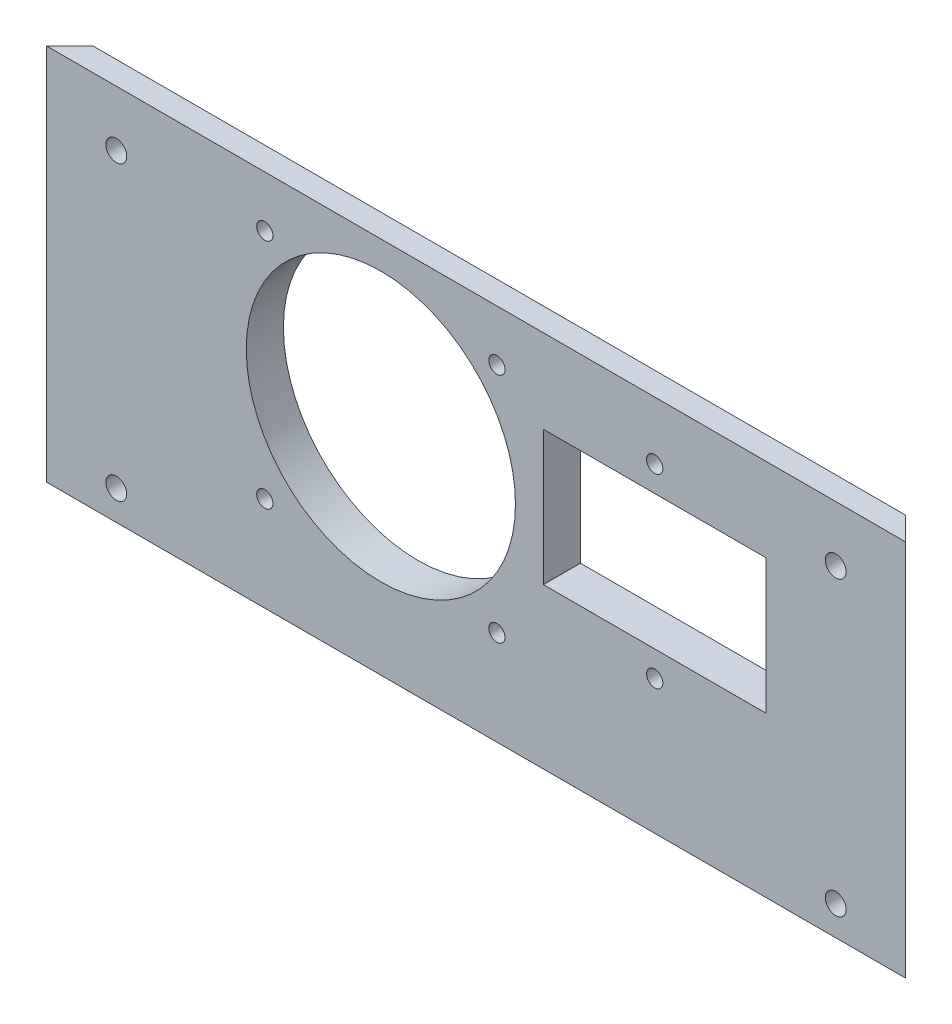
SolidWorks part; units mm, degrees
ref_plane "Front Plane" through (0, 0, 0) normal (0, 0, 1) x (1, 0, 0)
ref_plane "Top Plane" through (0, 0, 0) normal (0, 1, 0) x (1, 0, 0)
ref_plane "Right Plane" through (0, 0, 0) normal (1, 0, 0) x (0, 0, -1)
sketch "Sketch1" plane through (0, 0, 0) normal (0, 0, 1) x (1, 0, 0)
  line L0 (92.5, 84) -> (92.5, -37.3998) construction
  line L1 (0, 0) -> (185, 0)
  line L2 (0, 0) -> (0, 84)
  line L3 (0, 84) -> (185, 84)
  line L4 (185, 0) -> (185, 84)
  line L5 (0, 42) -> (185, 42) construction
  circle A0 centre (15, 9) radius 2.25
  circle A1 centre (170, 9) radius 2.25
  circle A4 centre (15, 72) radius 2.25
  circle A5 centre (170, 72) radius 2.25
  dimension "D3" = 15
  dimension "D5" = 4.5
  dimension "D1" = 84
  dimension "D2" = 185
  dimension "D4" = 9
  dimension "D6" = 2
  dimension "D7" = 12
extrude "Boss-Extrude1" add sketch "Sketch1" against normal blind 5
sketch "Sketch2" plane through (0, 0, -5) normal (0, 0, -1) x (-1, 0, 0)
  line L0 (0, 0) -> (-185, 0) construction
  line L1 (0, 0) -> (-185, 0) construction
  line L2 (0, 5) -> (-185, 5)
  line L3 (-185, 5) -> (-185, 84)
  line L4 (-185, 84) -> (0, 84)
  line L5 (0, 84) -> (0, 5)
  circle A1 centre (-15, 9) radius 2.25 construction
  circle A2 centre (-170, 9) radius 2.25 construction
  circle A5 centre (-15, 9) radius 2.25
  circle A6 centre (-170, 9) radius 2.25
  circle A8 centre (-15, 72) radius 2.25 construction
  circle A9 centre (-170, 72) radius 2.25 construction
  circle A10 centre (-15, 72) radius 2.25
  circle A11 centre (-170, 72) radius 2.25
  dimension "D1" = 5
extrude "Boss-Extrude2" add sketch "Sketch2" along normal blind 3
chamfer "Chamfer1" distance 8 angle 45 3 edges at (185, 44.5, -8) (0, 44.5, -8) (92.5, 84, -8)
chamfer "Chamfer3" distance 3 angle 45 1 edges at (92.5, 84, -8)
sketch "Sketch3" plane through (92.5, 0, -92.5) normal (0.7071, 0, -0.7071) x (-0.7071, 0, -0.7071)
  line L0 (-130.8148, 0) -> (-130.8148, 2.6)
  line L1 (-130.8148, 0) -> (-130.8148, 84) construction
  line L2 (-130.8148, 2.6) -> (-123.7437, 2.6)
  line L4 (-123.7437, 2.6) -> (-123.7437, 0)
  line L5 (-123.7437, 0) -> (-130.8148, 0)
  line L6 (-119.501, 5) -> (-123.7437, 5) construction
  dimension "D1" = 2.4
extrude "Cut-Extrude1" cut sketch "Sketch3" along direction (1, 0, 0) on the side against the normal through all
sketch "Sketch4" plane through (0, 0, 0) normal (0, 0, 1) x (1, 0, 0)
  line L0 (185, 84) -> (0, 84) construction
  line L1 (107, 37) -> (155, 37)
  line L2 (107, 37) -> (107, 66)
  line L3 (107, 66) -> (155, 66)
  line L4 (155, 37) -> (155, 66)
  line L5 (185, 2.6) -> (185, 84) construction
  line L6 (131, 71.5) -> (131, 31.5) construction
  line L7 (107, 51.5) -> (155, 51.5) construction
  line L8 (43, 49) -> (42, 49) construction
  line L9 (42, 49) -> (42, 78) construction
  line L10 (42, 78) -> (72, 78) construction
  line L11 (42, 73) -> (47, 73) construction
  line L12 (47, 73) -> (47, 78) construction
  circle A0 centre (72, 49) radius 29
  circle A1 centre (47, 73) radius 1.75
  circle A2 centre (97, 73) radius 1.75
  circle A3 centre (97, 23) radius 1.75
  circle A4 centre (47, 23) radius 1.75
  circle A5 centre (131, 71.5) radius 1.75
  circle A6 centre (131, 31.5) radius 1.75
  point P28 (131, 51.5)
  point P31 (131, 66)
  dimension "D5" = 58
  dimension "D6" = 35
  dimension "D8" = 5
  dimension "D11" = 3.5
  dimension "D16" = 0
  dimension "D1" = 29
  dimension "D2" = 48
  dimension "D3" = 18
  dimension "D4" = 30
  dimension "D7" = 35
  dimension "D9" = 5
  dimension "D10" = 1
  dimension "D14" = 40
  dimension "D15" = 0
  dimension "D12" = 2
  dimension "D13" = 2
extrude "Cut-Extrude2" cut sketch "Sketch4" against normal through all
